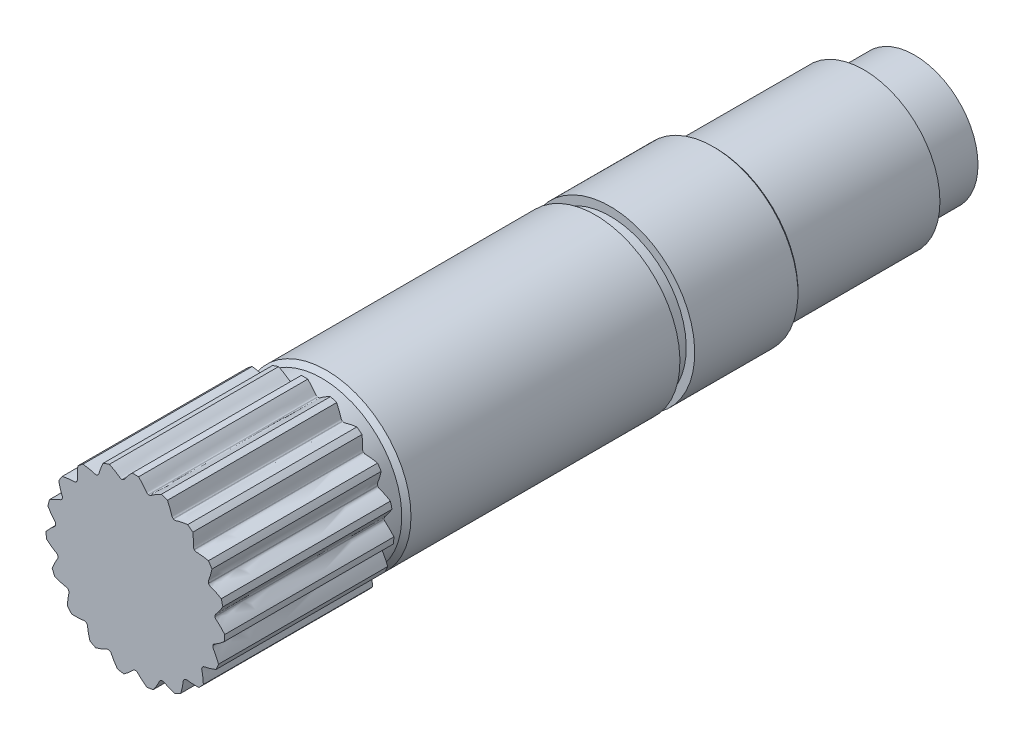
SolidWorks part; units mm, degrees
material "Alloy Steel"
ref_plane "Front Plane" through (0, 0, 0) normal (0, 0, 1) x (1, 0, 0)
ref_plane "Top Plane" through (0, 0, 0) normal (0, 1, 0) x (1, 0, 0)
ref_plane "Right Plane" through (0, 0, 0) normal (1, 0, 0) x (0, 0, -1)
sketch "Sketch12" plane through (0, 0, 0) normal (0, 0, 1) x (1, 0, 0)
  circle A0 centre (0, 0) radius 10
  dimension "D1" = 20
extrude "Shaft" add sketch "Sketch12" along normal mid plane 43
sketch "Sketch13" plane through (0, 0, 21.5) normal (0, 0, 1) x (1, 0, 0)
  circle A0 centre (0, 0) radius 9.4556
  dimension "D1" = 18.9113
extrude "Motor side relief" add sketch "Sketch13" along normal blind 1.587
sketch "Sketch14" plane through (0, 0, -21.5) normal (0, 0, -1) x (-1, 0, 0)
  circle A0 centre (0, 0) radius 8.3981
  dimension "D1" = 16.7963
sketch "Sketch15" plane through (0, 0, 23.087) normal (0, 0, 1) x (1, 0, 0)
  line L0 (5.7898, -7.4758) -> (5.8078, -7.4618)
  line L1 (5.8078, -7.4618) -> (5.8257, -7.4478)
  line L2 (7.9035, -5.1908) -> (7.9159, -5.1717)
  line L3 (7.9159, -5.1717) -> (7.9284, -5.1527)
  line L4 (9.1607, -2.3432) -> (9.1663, -2.3212)
  line L5 (9.1663, -2.3212) -> (9.1719, -2.2992)
  line L6 (9.4252, 0.7582) -> (9.4233, 0.7808)
  line L7 (9.4233, 0.7808) -> (9.4214, 0.8035)
  line L8 (8.6683, 3.7775) -> (8.6592, 3.7983)
  line L9 (8.6592, 3.7983) -> (8.6501, 3.8191)
  line L10 (6.9721, 6.3874) -> (6.9567, 6.4041)
  line L11 (6.9567, 6.4041) -> (6.9413, 6.4208)
  line L12 (4.5204, 8.3051) -> (4.5004, 8.316)
  line L13 (4.5004, 8.316) -> (4.4804, 8.3268)
  line L14 (1.5788, 9.3229) -> (1.5563, 9.3267)
  line L15 (1.5563, 9.3267) -> (1.5339, 9.3304)
  line L16 (-1.5339, 9.3304) -> (-1.5563, 9.3267)
  line L17 (-1.5563, 9.3267) -> (-1.5788, 9.3229)
  line L18 (-4.4804, 8.3268) -> (-4.5004, 8.316)
  line L19 (-4.5004, 8.316) -> (-4.5204, 8.3051)
  line L20 (-6.9413, 6.4208) -> (-6.9567, 6.4041)
  line L21 (-6.9567, 6.4041) -> (-6.9721, 6.3874)
  line L22 (-8.6501, 3.8191) -> (-8.6592, 3.7983)
  line L23 (-8.6592, 3.7983) -> (-8.6683, 3.7775)
  line L24 (-9.4214, 0.8035) -> (-9.4233, 0.7808)
  line L25 (-9.4233, 0.7808) -> (-9.4252, 0.7582)
  line L26 (-9.1719, -2.2992) -> (-9.1663, -2.3212)
  line L27 (-9.1663, -2.3212) -> (-9.1607, -2.3432)
  line L28 (-7.9284, -5.1527) -> (-7.9159, -5.1717)
  line L29 (-7.9159, -5.1717) -> (-7.9035, -5.1908)
  line L30 (-5.8257, -7.4478) -> (-5.8078, -7.4618)
  line L31 (-5.8078, -7.4618) -> (-5.7898, -7.4758)
  line L32 (-3.0917, -8.9359) -> (-3.0702, -8.9433)
  line L33 (-3.0702, -8.9433) -> (-3.0487, -8.9507)
  line L34 (-0.0227, -9.4556) -> (0, -9.4556)
  line L35 (0, -9.4556) -> (0.0227, -9.4556)
  line L36 (3.0487, -8.9507) -> (3.0702, -8.9433)
  line L37 (3.0702, -8.9433) -> (3.0917, -8.9359)
  arc A0 (4.6925, -9.4774) -> (5.3676, -9.1121) centre (0, 0) ccw
  arc A1 (7.5156, -7.4402) -> (8.0355, -6.8755) centre (0, 0) ccw
  arc A2 (9.5242, -4.5968) -> (9.8326, -3.8939) centre (0, 0) ccw
  arc A3 (10.5007, -1.2552) -> (10.5641, -0.4903) centre (0, 0) ccw
  arc A4 (10.3394, 2.2224) -> (10.1509, 2.9665) centre (0, 0) ccw
  arc A5 (9.0575, 5.4591) -> (8.6377, 6.1017) centre (0, 0) ccw
  arc A6 (6.7942, 8.1043) -> (6.1885, 8.5758) centre (0, 0) ccw
  arc A7 (3.7946, 9.8713) -> (3.0686, 10.1205) centre (0, 0) ccw
  arc A8 (0.3838, 10.5685) -> (-0.3838, 10.5685) centre (0, 0) ccw
  arc A9 (-3.0686, 10.1205) -> (-3.7946, 9.8713) centre (0, 0) ccw
  arc A10 (-6.1885, 8.5758) -> (-6.7942, 8.1043) centre (0, 0) ccw
  arc A11 (-8.6377, 6.1017) -> (-9.0575, 5.4591) centre (0, 0) ccw
  arc A12 (-10.1509, 2.9665) -> (-10.3394, 2.2224) centre (0, 0) ccw
  arc A13 (-10.5641, -0.4903) -> (-10.5007, -1.2552) centre (0, 0) ccw
  arc A14 (-9.8326, -3.8939) -> (-9.5242, -4.5968) centre (0, 0) ccw
  arc A15 (-8.0355, -6.8755) -> (-7.5156, -7.4402) centre (0, 0) ccw
  arc A16 (-5.3676, -9.1121) -> (-4.6925, -9.4774) centre (0, 0) ccw
  arc A17 (-2.1181, -10.3612) -> (-1.361, -10.4876) centre (0, 0) ccw
  arc A18 (1.361, -10.4876) -> (2.1181, -10.3612) centre (0, 0) ccw
  spline S0 degree 3 poles (3.0917, -8.9359) (3.1544, -8.9142) (3.2184, -8.911) (3.3396, -8.938) (3.397, -8.9729) (3.5767, -9.0624) (3.828, -9.1783) (4.24, -9.3384) (4.5379, -9.4334) (4.6925, -9.4774) knots 0 0 0 0 0.125 0.125 0.25 0.25 0.5 0.75 1 1 1 1
  spline S1 degree 3 poles (5.3676, -9.1121) (5.4153, -8.9586) (5.4987, -8.6572) (5.5901, -8.2247) (5.6305, -7.951) (5.6538, -7.7516) (5.656, -7.6845) (5.6997, -7.5682) (5.7374, -7.5164) (5.7898, -7.4758) knots 0 0 0 0 0.25 0.5 0.75 0.75 0.875 0.875 1 1 1 1
  spline S2 degree 3 poles (5.8257, -7.4478) (5.8779, -7.407) (5.9374, -7.3832) (6.0608, -7.3694) (6.1265, -7.3837) (6.3255, -7.41) (6.6008, -7.438) (7.0425, -7.4557) (7.3551, -7.4488) (7.5156, -7.4402) knots 0 0 0 0 0.125 0.125 0.25 0.25 0.5 0.75 1 1 1 1
  spline S3 degree 3 poles (8.0355, -6.8755) (8.0308, -6.7148) (8.0117, -6.4027) (7.9577, -5.964) (7.9071, -5.692) (7.8645, -5.4958) (7.8447, -5.4316) (7.8483, -5.3075) (7.8671, -5.2462) (7.9035, -5.1908) knots 0 0 0 0 0.25 0.5 0.75 0.75 0.875 0.875 1 1 1 1
  spline S4 degree 3 poles (7.9284, -5.1527) (7.9645, -5.0971) (8.013, -5.0552) (8.1253, -5.0021) (8.192, -4.9944) (8.3888, -4.9546) (8.6583, -4.8918) (9.0817, -4.765) (9.3752, -4.6571) (9.5242, -4.5968) knots 0 0 0 0 0.125 0.125 0.25 0.25 0.5 0.75 1 1 1 1
  spline S5 degree 3 poles (9.8326, -3.8939) (9.7759, -3.7434) (9.6566, -3.4544) (9.4631, -3.057) (9.3268, -2.8161) (9.2228, -2.6445) (9.1833, -2.5901) (9.1463, -2.4716) (9.1443, -2.4075) (9.1607, -2.3432) knots 0 0 0 0 0.25 0.5 0.75 0.75 0.875 0.875 1 1 1 1
  spline S6 degree 3 poles (9.1719, -2.2992) (9.188, -2.2349) (9.2203, -2.1795) (9.3092, -2.0928) (9.3699, -2.0638) (9.543, -1.9624) (9.7775, -1.8154) (10.1368, -1.558) (10.3793, -1.3606) (10.5007, -1.2552) knots 0 0 0 0 0.125 0.125 0.25 0.25 0.5 0.75 1 1 1 1
  spline S7 degree 3 poles (10.5641, -0.4903) (10.4617, -0.3663) (10.255, -0.1317) (9.9429, 0.1813) (9.7359, 0.3649) (9.5818, 0.4935) (9.5267, 0.532) (9.4533, 0.6322) (9.4305, 0.6921) (9.4252, 0.7582) knots 0 0 0 0 0.25 0.5 0.75 0.75 0.875 0.875 1 1 1 1
  spline S8 degree 3 poles (9.4214, 0.8035) (9.4158, 0.8695) (9.4284, 0.9324) (9.4844, 1.0433) (9.5323, 1.0904) (9.6631, 1.2426) (9.8372, 1.4577) (10.0935, 1.8179) (10.2588, 2.0833) (10.3394, 2.2224) knots 0 0 0 0 0.125 0.125 0.25 0.25 0.5 0.75 1 1 1 1
  spline S9 degree 3 poles (10.1509, 2.9665) (10.0138, 3.0504) (9.7422, 3.2052) (9.3453, 3.4) (9.0899, 3.5063) (8.9024, 3.5779) (8.8378, 3.5965) (8.7358, 3.6674) (8.6948, 3.7167) (8.6683, 3.7775) knots 0 0 0 0 0.25 0.5 0.75 0.75 0.875 0.875 1 1 1 1
  spline S10 degree 3 poles (8.6501, 3.8191) (8.6233, 3.8797) (8.6148, 3.9433) (8.6317, 4.0663) (8.6618, 4.1264) (8.7361, 4.3129) (8.8308, 4.5729) (8.9563, 4.9967) (9.0265, 5.3014) (9.0575, 5.4591) knots 0 0 0 0 0.125 0.125 0.25 0.25 0.5 0.75 1 1 1 1
  spline S11 degree 3 poles (8.6377, 6.1017) (8.4808, 6.1366) (8.1736, 6.1948) (7.735, 6.2502) (7.4588, 6.2678) (7.2583, 6.2747) (7.1911, 6.2713) (7.0717, 6.3052) (7.0169, 6.3385) (6.9721, 6.3874) knots 0 0 0 0 0.25 0.5 0.75 0.75 0.875 0.875 1 1 1 1
  spline S12 degree 3 poles (6.9413, 6.4208) (6.8963, 6.4695) (6.8676, 6.5268) (6.8437, 6.6487) (6.8526, 6.7153) (6.8624, 6.9158) (6.8676, 7.1925) (6.8486, 7.6341) (6.816, 7.9451) (6.7942, 8.1043) knots 0 0 0 0 0.125 0.125 0.25 0.25 0.5 0.75 1 1 1 1
  spline S13 degree 3 poles (6.1885, 8.5758) (6.0287, 8.5578) (5.7193, 8.5131) (5.2865, 8.4231) (5.0196, 8.3501) (4.8276, 8.2914) (4.7652, 8.2664) (4.6412, 8.2597) (4.5786, 8.2734) (4.5204, 8.3051) knots 0 0 0 0 0.25 0.5 0.75 0.75 0.875 0.875 1 1 1 1
  spline S14 degree 3 poles (4.4804, 8.3268) (4.422, 8.3582) (4.3763, 8.4031) (4.3141, 8.5106) (4.3009, 8.5765) (4.245, 8.7693) (4.1601, 9.0326) (3.9988, 9.4442) (3.8669, 9.7277) (3.7946, 9.8713) knots 0 0 0 0 0.125 0.125 0.25 0.25 0.5 0.75 1 1 1 1
  spline S15 degree 3 poles (3.0686, 10.1205) (2.9233, 10.0517) (2.6452, 9.9089) (2.2651, 9.6832) (2.0363, 9.5275) (1.8738, 9.4097) (1.8229, 9.3658) (1.7078, 9.3192) (1.6441, 9.3118) (1.5788, 9.3229) knots 0 0 0 0 0.25 0.5 0.75 0.75 0.875 0.875 1 1 1 1
  spline S16 degree 3 poles (1.5339, 9.3304) (1.4685, 9.3411) (1.4107, 9.3688) (1.3169, 9.4502) (1.283, 9.5083) (1.1676, 9.6725) (1.0018, 9.894) (0.7156, 10.2309) (0.4988, 10.4563) (0.3838, 10.5685) knots 0 0 0 0 0.125 0.125 0.25 0.25 0.5 0.75 1 1 1 1
  spline S17 degree 3 poles (-0.3838, 10.5685) (-0.4988, 10.4563) (-0.7156, 10.2309) (-1.0018, 9.894) (-1.1676, 9.6725) (-1.283, 9.5083) (-1.3169, 9.4502) (-1.4107, 9.3688) (-1.4685, 9.3411) (-1.5339, 9.3304) knots 0 0 0 0 0.25 0.5 0.75 0.75 0.875 0.875 1 1 1 1
  spline S18 degree 3 poles (-1.5788, 9.3229) (-1.6441, 9.3118) (-1.7078, 9.3192) (-1.8229, 9.3658) (-1.8738, 9.4097) (-2.0363, 9.5275) (-2.2651, 9.6832) (-2.6452, 9.9089) (-2.9233, 10.0517) (-3.0686, 10.1205) knots 0 0 0 0 0.125 0.125 0.25 0.25 0.5 0.75 1 1 1 1
  spline S19 degree 3 poles (-3.7946, 9.8713) (-3.8669, 9.7277) (-3.9988, 9.4442) (-4.1601, 9.0326) (-4.245, 8.7693) (-4.3009, 8.5765) (-4.3141, 8.5106) (-4.3763, 8.4031) (-4.422, 8.3582) (-4.4804, 8.3268) knots 0 0 0 0 0.25 0.5 0.75 0.75 0.875 0.875 1 1 1 1
  spline S20 degree 3 poles (-4.5204, 8.3051) (-4.5786, 8.2734) (-4.6412, 8.2597) (-4.7652, 8.2664) (-4.8276, 8.2914) (-5.0196, 8.3501) (-5.2865, 8.4231) (-5.7193, 8.5131) (-6.0287, 8.5578) (-6.1885, 8.5758) knots 0 0 0 0 0.125 0.125 0.25 0.25 0.5 0.75 1 1 1 1
  spline S21 degree 3 poles (-6.7942, 8.1043) (-6.816, 7.9451) (-6.8486, 7.6341) (-6.8676, 7.1925) (-6.8624, 6.9158) (-6.8526, 6.7153) (-6.8437, 6.6487) (-6.8676, 6.5268) (-6.8963, 6.4695) (-6.9413, 6.4208) knots 0 0 0 0 0.25 0.5 0.75 0.75 0.875 0.875 1 1 1 1
  spline S22 degree 3 poles (-6.9721, 6.3874) (-7.0169, 6.3385) (-7.0717, 6.3052) (-7.1911, 6.2713) (-7.2583, 6.2747) (-7.4588, 6.2678) (-7.735, 6.2502) (-8.1736, 6.1948) (-8.4808, 6.1366) (-8.6377, 6.1017) knots 0 0 0 0 0.125 0.125 0.25 0.25 0.5 0.75 1 1 1 1
  spline S23 degree 3 poles (-9.0575, 5.4591) (-9.0265, 5.3014) (-8.9563, 4.9967) (-8.8308, 4.5729) (-8.7361, 4.3129) (-8.6618, 4.1264) (-8.6317, 4.0663) (-8.6148, 3.9433) (-8.6233, 3.8797) (-8.6501, 3.8191) knots 0 0 0 0 0.25 0.5 0.75 0.75 0.875 0.875 1 1 1 1
  spline S24 degree 3 poles (-8.6683, 3.7775) (-8.6948, 3.7167) (-8.7358, 3.6674) (-8.8378, 3.5965) (-8.9024, 3.5779) (-9.0899, 3.5063) (-9.3453, 3.4) (-9.7422, 3.2052) (-10.0138, 3.0504) (-10.1509, 2.9665) knots 0 0 0 0 0.125 0.125 0.25 0.25 0.5 0.75 1 1 1 1
  spline S25 degree 3 poles (-10.3394, 2.2224) (-10.2588, 2.0833) (-10.0935, 1.8179) (-9.8372, 1.4577) (-9.6631, 1.2426) (-9.5323, 1.0904) (-9.4844, 1.0433) (-9.4284, 0.9324) (-9.4158, 0.8695) (-9.4214, 0.8035) knots 0 0 0 0 0.25 0.5 0.75 0.75 0.875 0.875 1 1 1 1
  spline S26 degree 3 poles (-9.4252, 0.7582) (-9.4305, 0.6921) (-9.4533, 0.6322) (-9.5267, 0.532) (-9.5818, 0.4935) (-9.7359, 0.3649) (-9.9429, 0.1813) (-10.255, -0.1317) (-10.4617, -0.3663) (-10.5641, -0.4903) knots 0 0 0 0 0.125 0.125 0.25 0.25 0.5 0.75 1 1 1 1
  spline S27 degree 3 poles (-10.5007, -1.2552) (-10.3793, -1.3606) (-10.1368, -1.558) (-9.7775, -1.8154) (-9.543, -1.9624) (-9.3699, -2.0638) (-9.3092, -2.0928) (-9.2203, -2.1795) (-9.188, -2.2349) (-9.1719, -2.2992) knots 0 0 0 0 0.25 0.5 0.75 0.75 0.875 0.875 1 1 1 1
  spline S28 degree 3 poles (-9.1607, -2.3432) (-9.1443, -2.4075) (-9.1463, -2.4716) (-9.1833, -2.5901) (-9.2228, -2.6445) (-9.3268, -2.8161) (-9.4631, -3.057) (-9.6566, -3.4544) (-9.7759, -3.7434) (-9.8326, -3.8939) knots 0 0 0 0 0.125 0.125 0.25 0.25 0.5 0.75 1 1 1 1
  spline S29 degree 3 poles (-9.5242, -4.5968) (-9.3752, -4.6571) (-9.0817, -4.765) (-8.6583, -4.8918) (-8.3888, -4.9546) (-8.192, -4.9944) (-8.1253, -5.0021) (-8.013, -5.0552) (-7.9645, -5.0971) (-7.9284, -5.1527) knots 0 0 0 0 0.25 0.5 0.75 0.75 0.875 0.875 1 1 1 1
  spline S30 degree 3 poles (-7.9035, -5.1908) (-7.8671, -5.2462) (-7.8483, -5.3075) (-7.8447, -5.4316) (-7.8645, -5.4958) (-7.9071, -5.692) (-7.9577, -5.964) (-8.0117, -6.4027) (-8.0308, -6.7148) (-8.0355, -6.8755) knots 0 0 0 0 0.125 0.125 0.25 0.25 0.5 0.75 1 1 1 1
  spline S31 degree 3 poles (-7.5156, -7.4402) (-7.3551, -7.4488) (-7.0425, -7.4557) (-6.6008, -7.438) (-6.3255, -7.41) (-6.1265, -7.3837) (-6.0608, -7.3694) (-5.9374, -7.3832) (-5.8779, -7.407) (-5.8257, -7.4478) knots 0 0 0 0 0.25 0.5 0.75 0.75 0.875 0.875 1 1 1 1
  spline S32 degree 3 poles (-5.7898, -7.4758) (-5.7374, -7.5164) (-5.6997, -7.5682) (-5.656, -7.6845) (-5.6538, -7.7516) (-5.6305, -7.951) (-5.5901, -8.2247) (-5.4987, -8.6572) (-5.4153, -8.9586) (-5.3676, -9.1121) knots 0 0 0 0 0.125 0.125 0.25 0.25 0.5 0.75 1 1 1 1
  spline S33 degree 3 poles (-4.6925, -9.4774) (-4.5379, -9.4334) (-4.24, -9.3384) (-3.828, -9.1783) (-3.5767, -9.0624) (-3.397, -8.9729) (-3.3396, -8.938) (-3.2184, -8.911) (-3.1544, -8.9142) (-3.0917, -8.9359) knots 0 0 0 0 0.25 0.5 0.75 0.75 0.875 0.875 1 1 1 1
  spline S34 degree 3 poles (-3.0487, -8.9507) (-2.986, -8.972) (-2.9335, -9.0088) (-2.8544, -9.1046) (-2.8306, -9.1674) (-2.7437, -9.3484) (-2.6166, -9.5942) (-2.3898, -9.9736) (-2.2131, -10.2315) (-2.1181, -10.3612) knots 0 0 0 0 0.125 0.125 0.25 0.25 0.5 0.75 1 1 1 1
  spline S35 degree 3 poles (-1.361, -10.4876) (-1.229, -10.3957) (-0.9781, -10.2091) (-0.6404, -9.9239) (-0.4404, -9.7327) (-0.2995, -9.5898) (-0.2565, -9.5381) (-0.1506, -9.4732) (-0.089, -9.4555) (-0.0227, -9.4556) knots 0 0 0 0 0.25 0.5 0.75 0.75 0.875 0.875 1 1 1 1
  spline S36 degree 3 poles (0.0227, -9.4556) (0.089, -9.4555) (0.1506, -9.4732) (0.2565, -9.5381) (0.2995, -9.5898) (0.4404, -9.7327) (0.6404, -9.9239) (0.9781, -10.2091) (1.229, -10.3957) (1.361, -10.4876) knots 0 0 0 0 0.125 0.125 0.25 0.25 0.5 0.75 1 1 1 1
  spline S37 degree 3 poles (2.1181, -10.3612) (2.2131, -10.2315) (2.3898, -9.9736) (2.6166, -9.5942) (2.7437, -9.3484) (2.8306, -9.1674) (2.8544, -9.1046) (2.9335, -9.0088) (2.986, -8.972) (3.0487, -8.9507) knots 0 0 0 0 0.25 0.5 0.75 0.75 0.875 0.875 1 1 1 1
extrude "Motor spline" add sketch "Sketch15" along normal blind 20
chamfer "Chamfer3" distance 1 angle 45 1 edges at (10, 0, 21.5)
sketch "Sketch23" plane through (0, 0, -31.5) normal (-0.9227, 0.3855, 0) x (-0.3855, -0.9227, 0)
  line L0 (10, 20.2042) -> (9, 20.2042)
  line L1 (9, 20.2042) -> (9, 18.4542)
  line L2 (9, 18.4542) -> (10, 18.4542)
  line L3 (10, 18.4542) -> (10, 20.2042)
  line L4 (10, 10) -> (10, 52) construction
  line L5 (-13.85, 20.2042) -> (13.85, 20.2042) construction
  line L7 (0, 185.3358) -> (0, -121.609) construction
  dimension "D1" = 1.75
  dimension "D2" = 1
revolve "snap ring" cut sketch "Sketch23" angle 360 about L7
sketch "Sketch24" plane through (0, 0, 0) normal (0, 1, 0) x (1, 0, 0)
  line L3 (10, 21.5) -> (10, 25.5)
  line L5 (7.5, 43.5) -> (7.5, 49.5)
  line L6 (7.5, 49.5) -> (0, 49.5)
  line L7 (0, 49.5) -> (0, 21.5)
  line L8 (10, 21.5) -> (-10, 21.5) construction
  line L9 (0, 21.5) -> (10, 21.5)
  line L10 (0, 0) -> (0, 49.7252) construction
  line L12 (7.5, 43.5) -> (9, 43.5)
  line L14 (10, 25.5) -> (9, 25.5)
  line L15 (9, 25.5) -> (9, 43.5)
  dimension "D1" = 15
  dimension "D2" = 22
  dimension "D3" = 4
  dimension "D8" = 6
revolve "Revolve1" add sketch "Sketch24" angle 360 about L10
chamfer "Chamfer4" distance 1 angle 25 2 edges at (9, 0, -43.5) (7.5, 0, -49.5) first distance on face at (7.5, 0, -43.5) first distance on face at (7.5, 0, -49.5)
chamfer "Chamfer5" distance 0.25 angle 45 1 edges at (10, 0, -25.5)
